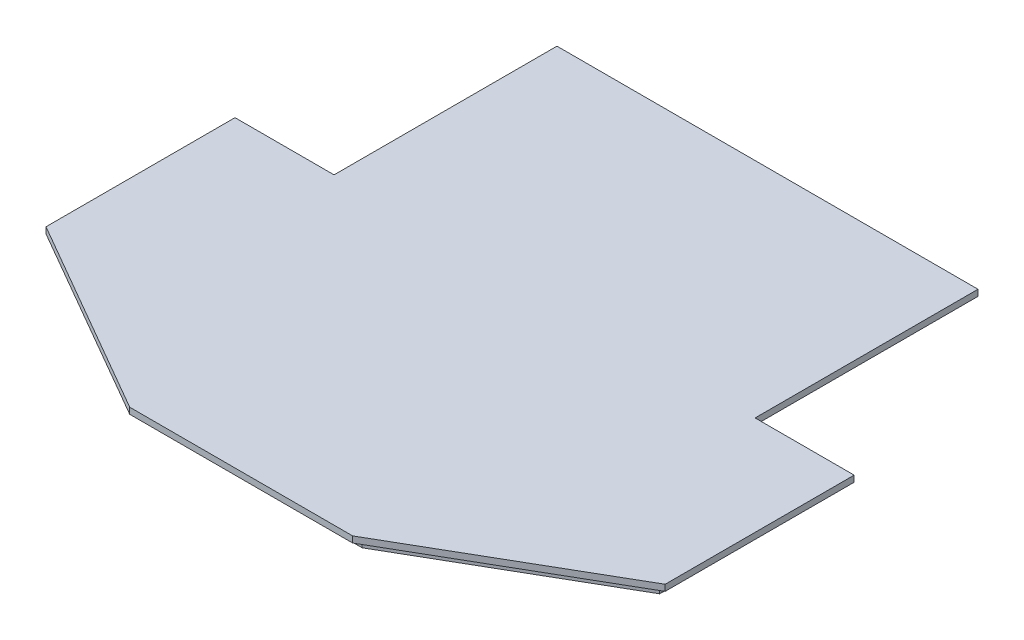
SolidWorks part; units mm, degrees
ref_plane "前视基准面" through (0, 0, 0) normal (0, 0, 1) x (1, 0, 0)
ref_plane "上视基准面" through (0, 0, 0) normal (0, 1, 0) x (1, 0, 0)
ref_plane "右视基准面" through (0, 0, 0) normal (1, 0, 0) x (0, 0, -1)
other "Configuration Table"
sketch "草图1" plane through (0, 0, 0) normal (0, 1, 0) x (1, 0, 0)
  line L0 (-100, -200) -> (0, -200) construction
  line L1 (0, -200) -> (0, 0) construction
  line L2 (-100, -133.0496) -> (-36, -170)
  line L3 (-36, -170) -> (36, -170)
  line L4 (-100, -72) -> (-100, -133.0496)
  line L5 (-100, -72) -> (-68, -72)
  line L6 (-68, -72) -> (-68, 0)
  line L7 (-68, 0) -> (68, 0)
  line L8 (68, -72) -> (68, 0)
  line L9 (100, -72) -> (68, -72)
  line L10 (100, -72) -> (100, -133.0496)
  line L11 (100, -133.0496) -> (36, -170)
  point P7 (0, -170)
  point P13 (0, -70)
  point P15 (0, -170)
  point P16 (0, 0)
  dimension "D1" = 150
  dimension "D2" = 30
  dimension "D3" = 73.9008
  dimension "D4" = 36
  dimension "D5" = 68
  dimension "D6" = 72
  dimension "D7" = 100
  dimension "D8" = 32
  dimension "D9" = 170
  dimension "D10" = 133.0496
extrude "凸台-拉伸1" add sketch "草图1" along normal blind 2
sketch "草图2" plane through (0, 0, 0) normal (0, 1, 0) x (1, 0, 0)
  line L0 (95.8, -76.2) -> (63.8, -76.2)
  line L1 (63.8, -76.2) -> (63.8, -4.2)
  line L2 (63.8, -4.2) -> (-63.8, -4.2)
  line L3 (-63.8, -4.2) -> (-63.8, -76.2)
  line L4 (-63.8, -76.2) -> (-95.8, -76.2)
  line L5 (-95.8, -76.2) -> (-95.8, -130.6247)
  line L6 (-95.8, -130.6247) -> (-34.8746, -165.8)
  line L7 (-34.8746, -165.8) -> (34.8746, -165.8)
  line L8 (34.8746, -165.8) -> (95.8, -130.6247)
  line L9 (95.8, -130.6247) -> (95.8, -76.2)
  line L11 (0, 0) -> (0, -170) construction
  line L12 (-36, -170) -> (36, -170) construction
  line L13 (68, -72) -> (68, 0) construction
  line L14 (100, -72) -> (68, -72) construction
  line L15 (100, -133.0496) -> (100, -72) construction
  line L16 (36, -170) -> (100, -133.0496) construction
  line L17 (-100, -133.0496) -> (-36, -170) construction
  line L18 (-100, -72) -> (-100, -133.0496) construction
  line L19 (-68, -72) -> (-100, -72) construction
  line L20 (-68, 0) -> (-68, -72) construction
  dimension "D1" = 127.6
  dimension "D2" = 4.2
  dimension "D3" = 63.8
  dimension "D4" = 4.2
  dimension "D5" = 4.2
  dimension "D6" = 4.2
  dimension "D7" = 4.2
  dimension "D8" = 4.2
  dimension "D9" = 4.2
  dimension "D10" = 4.2
  dimension "D11" = 4.2
  dimension "D12" = 4.2
  dimension "D13" = 72
extrude "凸台-拉伸2" add sketch "草图2" against normal blind 4
shell "抽壳4" thickness 4 removed face at (0, -4, 90.6049)
